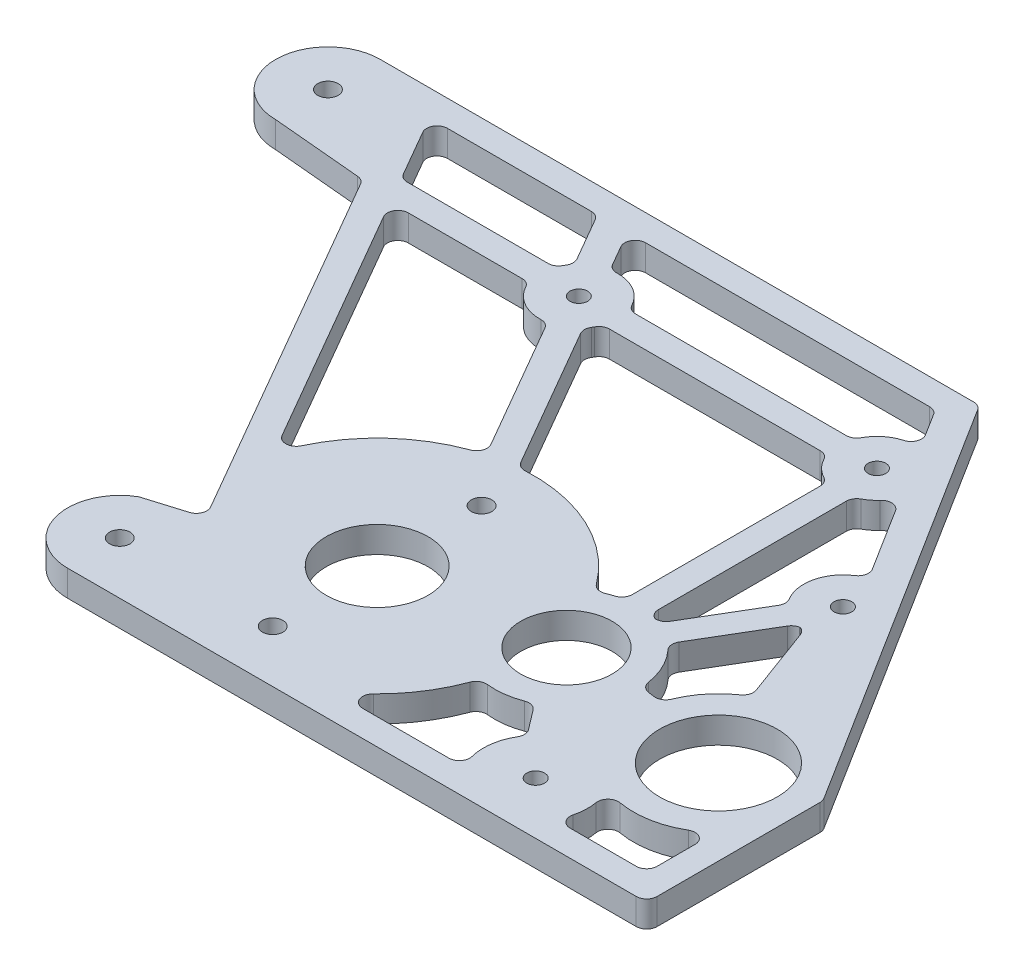
SolidWorks part; units mm, degrees
ref_plane "Front Plane" through (0, 0, 0) normal (0, 0, 1) x (1, 0, 0)
ref_plane "Top Plane" through (0, 0, 0) normal (0, 1, 0) x (1, 0, 0)
ref_plane "Right Plane" through (0, 0, 0) normal (1, 0, 0) x (0, 0, -1)
sketch "Sketch1" plane through (0, 0, 0) normal (0, 1, 0) x (1, 0, 0)
  line L0 (-190.7858, 72.591) -> (-106.965, -72.591)
  line L1 (-190.7858, 72.591) -> (190.7858, 72.591)
  line L2 (-190.7858, 72.591) -> (-190.7858, -72.591)
  line L3 (-190.7858, -72.591) -> (190.7858, -72.591)
  line L4 (190.7858, 72.591) -> (190.7858, -72.591)
  line L5 (-190.7858, 72.591) -> (190.7858, -72.591) construction
  line L6 (-190.7858, -72.591) -> (190.7858, 72.591) construction
  line L7 (-161.4564, 72.591) -> (-77.6356, -72.591)
  line L8 (-176.1211, 72.591) -> (-92.3003, -72.591) construction
  line L9 (-62.4429, -34.491) -> (-22.2218, -28.6714) construction
  line L10 (-22.2218, -28.6714) -> (20.5643, -34.491) construction
  line L11 (20.5643, -34.491) -> (-62.4429, -34.491) construction
  line L12 (47.5645, 72.591) -> (47.5645, -72.591)
  line L13 (-168.7887, 47.191) -> (-145.5814, 45.0947)
  line L14 (-105.9826, -48.8924) -> (-93.5106, -45.0947)
  circle A0 centre (-62.4429, -34.491) radius 32.2072
  circle A1 centre (-62.4429, -34.491) radius 12.3825
  circle A2 centre (-62.4429, -9.091) radius 2.4892
  circle A3 centre (-62.4429, -59.891) radius 2.4892
  circle A4 centre (-22.2218, -28.6714) radius 11.1252
  circle A5 centre (20.5643, -34.491) radius 14.3002
  circle A6 centre (-168.7887, 59.891) radius 2.4892
  circle A7 centre (-99.6326, -59.891) radius 2.4892
  circle A8 centre (-168.7887, 59.891) radius 12.7
  circle A9 centre (-99.6326, -59.891) radius 12.7
  point P0 (0, 0)
  dimension "D2" = 120
  dimension "D5" = 64.4144
  dimension "D6" = 24.765
  dimension "D7" = 4.9784
  dimension "D8" = 4.9784
  dimension "D9" = 50.8
  dimension "D10" = 25.4
  dimension "D11" = 12.7
  dimension "D15" = 22.2504
  dimension "D16" = 28.6004
  dimension "D18" = 4.9784
  dimension "D19" = 4.9784
  dimension "D20" = 12.7
  dimension "D21" = 12.7
  dimension "D22" = 25.4
  dimension "D23" = 31.75
  dimension "D1" = 145.1819
  dimension "D3" = 25.4
  dimension "D4" = 12.7
  dimension "D12" = 40.64
  dimension "D13" = 43.18
  dimension "D14" = 83.0072
  dimension "D17" = 27.0002
  dimension "D24" = 31.75
  dimension "D25" = 125.161
  dimension "D26" = 23.3018
extrude "Boss-Extrude1" add sketch "Sketch1" along normal blind 6.35 contours A4 A0 L7 L3 L12 L1 A5 | A4 A0 A3 A2 A1 | A9 L14 A7 | A9 L7 L14 | A9 L3 L7 | A8 A6 | A8 L13 L7 | A8 L7 L1 region at (-179.4762, 0, -66.0614) region at (-162.2256, 0, -71.2586) region at (-111.5529, 0, 56.6969) region at (-154.6803, 0, -50.934) region at (-75.6062, 0, 6.0972) region at (-35.8851, 0, -14.6154) region at (-85.7245, 0, 67.9208) region at (-94.2255, 0, 47.5186)
sketch "Sketch2" plane through (0, 6.35, 0) normal (0, 1, 0) x (1, 0, 0)
  line L0 (-145.5814, 45.0947) -> (-93.5106, -45.0947)
  line L1 (-154.124, 72.591) -> (-70.3032, -72.591)
  line L2 (-168.7887, 72.591) -> (47.5645, 72.591) construction
  line L3 (-99.6326, -72.591) -> (47.5645, -72.591) construction
  line L4 (-150.4579, 66.241) -> (47.5645, 66.241)
  line L5 (47.5645, 72.591) -> (47.5645, -72.591) construction
  line L6 (41.2145, 72.591) -> (41.2145, -72.591)
  line L7 (-73.9694, -66.241) -> (41.2145, -66.241)
  line L8 (-62.4429, -9.091) -> (-105.9359, 66.241) construction
  line L9 (-22.2218, -28.6714) -> (-22.2218, 66.241) construction
  line L10 (20.5643, -34.491) -> (20.5643, -66.241) construction
  line L11 (-22.2218, -28.6714) -> (1.5143, -59.891) construction
  line L12 (-22.2218, -28.6714) -> (20.5643, -34.491) construction
  line L13 (-139.2615, 46.8482) -> (41.2145, 46.8482) construction
  line L14 (-141.0946, 50.0232) -> (41.2145, 50.0232)
  line L15 (-137.4284, 43.6732) -> (41.2145, 43.6732)
  line L16 (-109.602, 66.241) -> (-72.6391, 2.2194)
  line L17 (-102.2697, 66.241) -> (-66.0124, 3.4415)
  line L18 (-25.3968, 66.241) -> (-25.3968, -11.487)
  line L19 (-19.0468, 66.241) -> (-19.0468, -11.487)
  line L20 (-4.7663, -27.8414) -> (0.7737, -28.5949)
  line L21 (-5.6221, -34.1334) -> (-0.0821, -34.887)
  line L22 (34.8645, 72.591) -> (34.8645, -72.591)
  line L23 (-14.3487, -44.2726) -> (-8.4556, -52.0238)
  line L24 (-9.2938, -40.4294) -> (-3.4006, -48.1806)
  line L25 (-19.0468, 66.241) -> (34.8645, -19.5935)
  line L26 (-27.416, 66.241) -> (22.9704, -13.9814)
  line L27 (-13.2415, 43.6732) -> (22.9704, -13.9814) construction
  line L28 (4.8645, 14.8459) -> (-19.0468, -0.1724) construction
  line L29 (-19.0468, 66.241) -> (-23.0351, 72.591)
  line L30 (-27.416, 66.241) -> (-31.4043, 72.591)
  line L31 (34.8645, -19.5935) -> (47.5645, -39.8137)
  line L32 (2.8001, 13.5493) -> (-22.2218, -28.6714) construction
  line L33 (2.8001, 13.5493) -> (20.5643, -34.491) construction
  line L34 (-4.5097, 7.4426) -> (-16.192, -12.2694)
  line L35 (0.953, 4.2051) -> (-10.7292, -15.5069)
  line L36 (2.9367, 4.0253) -> (10.5095, -16.454)
  line L37 (8.8926, 6.2276) -> (16.4653, -14.2517)
  circle A0 centre (-62.4429, -34.491) radius 38.1
  circle A1 centre (-22.2218, -28.6714) radius 17.4752
  circle A2 centre (20.5643, -34.491) radius 20.6502
  circle A3 centre (1.5143, -59.891) radius 2.1527
  circle A4 centre (1.5143, -59.891) radius 12.7
  circle A5 centre (-94.7395, 46.8482) radius 2.1527
  circle A6 centre (-94.7395, 46.8482) radius 9.525
  circle A7 centre (-22.2218, 46.8482) radius 2.1527
  circle A8 centre (-22.2218, 46.8482) radius 9.525
  circle A9 centre (2.8001, 13.5493) radius 9.525
  circle A10 centre (2.8001, 13.5493) radius 2.1527
  point P68 (-13.2415, 43.6732)
  line M27 (-99.6326, -72.591) -> (47.5645, -72.591)
  line M28 (47.5645, -72.591) -> (47.5645, 72.591)
  line M29 (47.5645, 72.591) -> (-168.7887, 72.591)
  dimension "D5" = 34.9504
  dimension "D6" = 41.3004
  dimension "D7" = 4.3053
  dimension "D9" = 25.4
  dimension "D11" = 4.3053
  dimension "D12" = 19.05
  dimension "D13" = 4.3053
  dimension "D14" = 19.05
  dimension "D21" = 19.05
  dimension "D22" = 4.3053
  dimension "D1" = 6.35
  dimension "D2" = 6.35
  dimension "D3" = 6.35
  dimension "D4" = 6.35
  dimension "D8" = 19.05
  dimension "D10" = 1.7536
  dimension "D15" = 6.35
  dimension "D16" = 6.35
  dimension "D17" = 6.35
  dimension "D18" = 6.35
  dimension "D19" = 12.7
  dimension "D20" = 6.35
  dimension "D23" = 6.35
  dimension "D24" = 6.35
extrude "Cut-Extrude2" cut sketch "Sketch2" against normal through all contours L6 L31 L4 M28 | L6 L4 M29 M28 | L4 L22 L14 L6 | L22 L4 L6 M29 | L29 L4 L22 M29 | L4 L25 L14 L22 | L14 L25 L15 L22 | L14 L22 L15 L6 | L15 L25 L22 | A2 L31 L6 L15 L22 | L31 L6 M27 M28 | A4 L7 L22 A2 | A4 L23 A1 A0 L7 | A9 L35 A1 L20 A2 L36 | A9 L26 A8 L19 A1 L34 | A8 L15 A6 L17 A0 A1 L18 | A8 L18 L26 L4 L17 A6 L14 | A6 L16 L4 L1 L14 | A6 L15 L1 A0 L16 | A5 | A7 | A8 L26 L18 | A10 | A3 | L31 A2 region at (-125.5477, 6.35, -58.1926) region at (-61.2079, 6.35, -58.6096) region at (6.8999, 6.35, -69.4537) region at (-103.6381, 6.35, -17.0075) region at (-24.0244, 6.35, -58.4944) region at (10.3668, 6.35, -58.4141) region at (38.0395, 6.35, -69.416) region at (38.0395, 6.35, -58.1321) region at (13.9831, 6.35, -46.8988) region at (44.3895, 6.35, -69.416) region at (44.4424, 6.35, -15.699) region at (38.0395, 6.35, -46.8482) region at (21.6189, 6.35, -22.5843) region at (-21.5834, 6.35, 57.1732) region at (-50.2878, 6.35, -22.0192) region at (38.1214, 6.35, -9.7689) region at (-12.5353, 6.35, -16.8952) region at (44.248, 6.35, 53.5622) region at (37.7382, 6.35, 23.7043) region at (24.8714, 6.35, 59.9323) region at (0.0693, 6.35, 13.136) region at (1.5143, 6.35, 59.891) region at (-94.7395, 6.35, -46.8482) region at (-22.2218, 6.35, -46.8482) region at (2.8001, 6.35, -13.5493)
fillet "Fillet1" radius 2.54 49 edges at (-93.5106, 3.175, 45.0947) (-26.0368, 3.175, 45.7251) (-14.3487, 3.175, 44.2726) (-8.4556, 3.175, 52.0238) (-9.4843, 3.175, 66.241) (-41.3824, 3.175, 66.241) (41.2145, 3.175, 72.591) (34.8645, 3.175, 66.241) (12.5128, 3.175, 66.241) (34.8645, 3.175, 49.3884) (12.4865, 3.175, 53.4957) (-4.7663, 3.175, 27.8414) (0.7737, 3.175, 28.5949) (10.5095, 3.175, 16.454) (-10.7292, 3.175, 15.5069) (2.9367, 3.175, -4.0253) (0.953, 3.175, -4.2051) (-0.0329, 3.175, -22.6432) (-4.5097, 3.175, -7.4426) (-19.0468, 3.175, 11.487) (-16.192, 3.175, 12.2694) (-13.2415, 3.175, -43.6732) (-19.0468, 3.175, -37.868) (-25.3968, 3.175, 11.487) (-30.7142, 3.175, 13.3985) (-66.0124, 3.175, -3.4415) (-25.3968, 3.175, -37.868) (-31.202, 3.175, -43.6732) (-31.202, 3.175, -50.0232) (-21.1825, 3.175, -56.3164) (-27.416, 3.175, -66.241) (-87.4997, 3.175, -40.6586) (-85.7592, 3.175, -43.6732) (-102.2697, 3.175, -66.241) (-85.7592, 3.175, -50.0232) (-96.48, 3.175, -56.2129) (-98.8271, 3.175, 23.1861) (-72.6391, 3.175, -2.2194) (-92.999, 3.175, -37.4836) (-103.7197, 3.175, -43.6732) (-137.4284, 3.175, -43.6732) (-145.5814, 3.175, -45.0947) (-109.602, 3.175, -66.241) (-101.9792, 3.175, -53.0379) (-103.7197, 3.175, -50.0232) (-150.4579, 3.175, -66.241) (-141.0946, 3.175, -50.0232) (-23.0351, 3.175, -72.591) (41.2145, 3.175, 29.7036)
